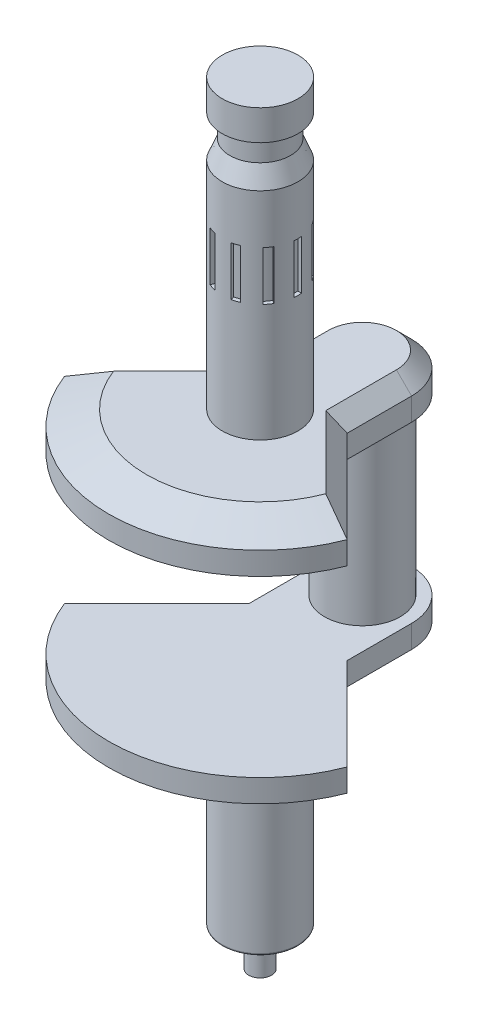
SolidWorks part; units mm, degrees
material "AISI 4340 Steel, normalized"
ref_plane "Front Plane" through (0, 0, 0) normal (1, 0, 0) x (0, 1, 0)
ref_plane "Top Plane" through (0, 0, 0) normal (0, 0, 1) x (0, 1, 0)
ref_plane "Right Plane" through (0, 0, 0) normal (0, 1, 0) x (-1, 0, 0)
sketch "Sketch1" plane through (0, 0, 0) normal (1, 0, 0) x (0, 1, 0)
  line L0 (-74.0817, 0) -> (114.0865, 0) construction
  line L1 (0, 53.0046) -> (0, -53.1977) construction
  line L2 (0, 10) -> (57, 10)
  line L3 (57, 10) -> (62, 8)
  line L4 (62, 8) -> (68, 8)
  line L5 (68, 8) -> (68, 10)
  line L6 (68, 10) -> (76, 10)
  line L7 (76, 10) -> (76, 0)
  line L8 (0, 10) -> (0, 0)
  line L9 (0, 0) -> (76, 0)
  line L10 (62, 8) -> (62, 0)
  line L11 (68, 8) -> (68, 0)
  dimension "D1" = 76
  dimension "D2" = 8
  dimension "D3" = 6
  dimension "D4" = 5
  dimension "D5" = 2
  dimension "D6" = 20
  dimension "D7" = 20
revolve "Revolve1" add sketch "Sketch1" angle 360 about L0 region at (0, 30.7615, 4.9648) region at (0, 65, 4) region at (0, 72, 5)
sketch "Sketch2" plane through (0, 0, 0) normal (1, 0, 0) x (0, 1, 0)
  line L0 (57, -10) -> (57, 10) construction
  line L1 (31, 1) -> (44, 1)
  line L2 (31, 1) -> (31, -1)
  line L3 (31, -1) -> (44, -1)
  line L4 (44, 1) -> (44, -1)
  dimension "D1" = 13
  dimension "D2" = 2
  dimension "D3" = 1
  dimension "D4" = 13
extrude "Cut-Extrude1" cut sketch "Sketch2" against normal blind 1 from surface contours L3 L4 L1 L2 starting at face at (0, 57, -10)
pattern_circular "CirPattern1" count 10 over 360 about axis through (0, 57, 0) along (0, -1, 0) of "Cut-Extrude1"
sketch "Sketch3" plane through (0, 0, 0) normal (0, -1, 0) x (1, 0, 0)
  line L0 (0, 40) -> (0, -40) construction
  line L1 (-36.6108, 0) -> (46.2229, 0) construction
  line L2 (-13, -10) -> (-39.6379, 16.6379)
  line L4 (-13, -10) -> (-13, -27)
  line L5 (-13, -27) -> (13, -27) construction
  line L6 (13, -10) -> (13, -27)
  line L7 (13, -10) -> (39.6379, 16.6379)
  line L8 (-15.3008, -10) -> (26.7001, -10) construction
  arc A1 (37.3409, 14.3409) -> (-37.3409, 14.3409) centre (0, 0) ccw
  circle A2 centre (0, 0) radius 10 construction
  arc A3 (-13, -27) -> (13, -27) centre (0, -27) ccw
  point P9 (0, -27)
  circle M10 centre (0, 0) radius 10
  dimension "D2" = 26
  dimension "D4" = 80
  dimension "D1" = 27
  dimension "D3" = 26
  dimension "D5" = 270
extrude "Boss-Extrude1" add sketch "Sketch3" along normal blind 10 separate body contours L4 A3 L6 L7 A1 L2 M10 | M10 region at (-24.3966, 0, 2.9443) region at (0, 0, 0)
chamfer "Chamfer2" distance 4 angle 45 3 edges at (-13, 0, -18.5) (13, 0, -18.5) (0, 0, -40)
chamfer "Chamfer6" distance 10 distance2 4 1 edges at (0, 0, 40) first distance on face at (0, 0, -6.1099)
chamfer "Chamfer3" distance 4 angle 45 1 edges at (19.1628, 0, -3.8372)
chamfer "Chamfer5" distance 4 angle 45 1 edges at (-19.1628, 0, -3.8372)
move or copy body "Body-Move/Copy1" bodies to move or copy 104 copy yes number of copies 1 translate (0, -36, 0) parameters "D1"=0, "D2"=36, "D3"=0
move or copy body "Body-Move/Copy2" bodies to move or copy 105 copy no rotation origin (0, -51, 0) rotation axis (0, 0, 1) rotation angle 180
sketch "Sketch5" plane through (0, -10, 0) normal (0, -1, 0) x (1, 0, 0)
  circle A2 centre (0, -27) radius 10
  arc A3 (-13, -27) -> (13, -27) centre (0, -27) ccw construction
  dimension "D1" = 20
extrude "Boss-Extrude2" add sketch "Sketch5" along normal blind 46
sketch "Sketch6" plane through (0, -66, 0) normal (0, -1, 0) x (1, 0, 0)
  circle A0 centre (0, 0) radius 10
  circle A1 centre (0, 0) radius 3
  dimension "D1" = 20
  dimension "D2" = 6
extrude "Boss-Extrude3" add sketch "Sketch6" along normal blind 52 contours A0
extrude "Boss-Extrude4" add sketch "Sketch6<3>" along normal blind 10 from surface contours A1 starting at face at (10, -118, 0)
sketch "Sketch6<3>" plane through (0, -66, 0) normal (0, -1, 0) x (1, 0, 0) same geometry as "Sketch6"
fillet "Fillet1" radius 0.5 1 edges at (10, -118, 0)
combine bodies "Combine1" operation type add bodies to combine 103 109
ref_axis "Axis1" through (0, 86.2, 0) along (0, -1, 0)
ref_axis "Axis2" through (0, -56, -27) along (0, 1, 0)
